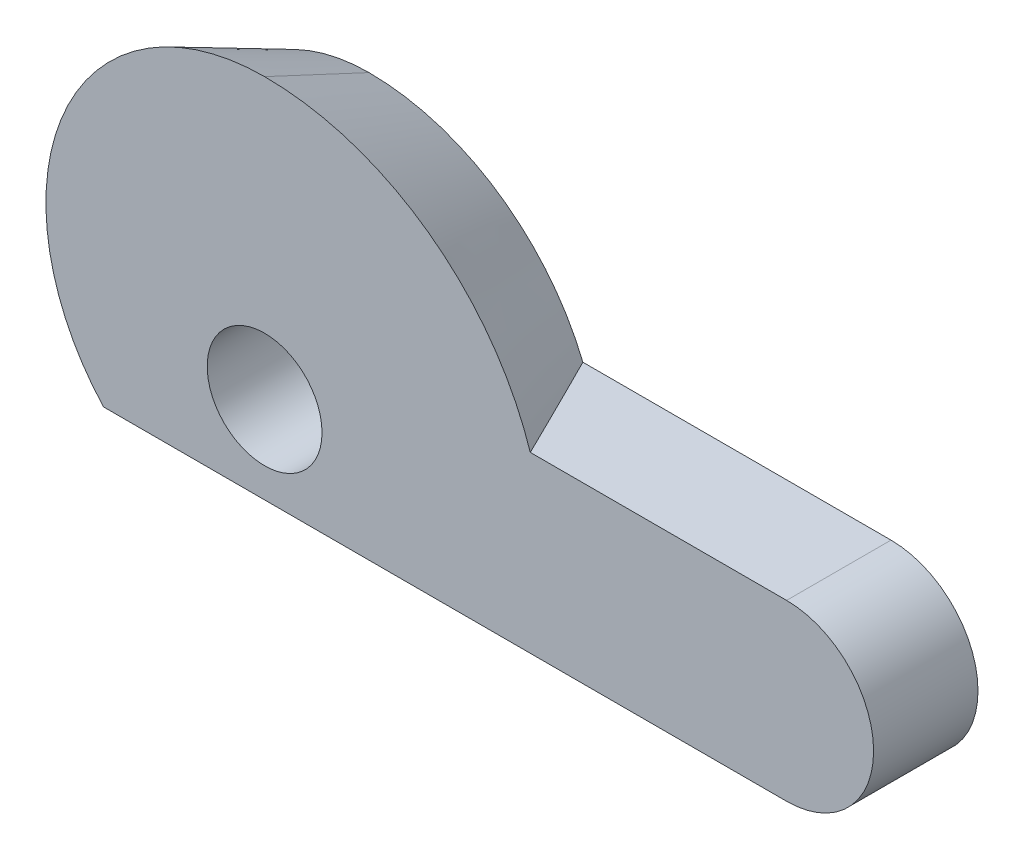
SolidWorks part; units mm, degrees
ref_plane "Plano frontal" through (0, 0, 0) normal (0, 0, 1) x (1, 0, 0)
ref_plane "Plano superior" through (0, 0, 0) normal (0, 1, 0) x (1, 0, 0)
ref_plane "Plano direito" through (0, 0, 0) normal (1, 0, 0) x (0, 0, -1)
sketch "Esboço2" plane through (0, 0, 0) normal (0, 0, 1) x (1, 0, 0)
  line L0 (15, 2.5) -> (8.124, 2.5)
  line L1 (15, -2.5) -> (4.3301, -2.5)
  line L2 (0, 0) -> (0, -5) construction
  line L3 (0, 0) -> (-5, 0) construction
  line L5 (-5.2806, 0) -> (-8.5, 0) construction
  arc A0 (15, -2.5) -> (15, 2.5) centre (15, 0) ccw
  circle A1 centre (0, 0) radius 1.65
  circle A2 centre (0, 0) radius 5 construction
  circle A3 centre (0, 0) radius 8.5 construction
  arc A4 (0, 8.5) -> (0, -5) centre (0, 1.75) ccw
  arc A5 (0, 8.5) -> (8.124, 2.5) centre (0, 0) cw
  arc A6 (0, -5) -> (4.3301, -2.5) centre (0, 0) ccw
  spline S0 degree 3 poles (4.3301, -2.5) (4.6958, -3.7346) (-0.8872, -5.2567) (2.4979, -4.9771) (-11.313, -5.0395) (-8.313, -3.1832) (-6.812, 0.9241) (-3.3405, 8.0667) (-0.7946, 8.4778) (2.5404, 8.3761) (5.4161, 6.8241) (7.7178, 4.2775) (8.124, 2.5) knots 0 0 0 0 0.107318 0.196785 0.229802 0.473899 0.513503 0.613354 0.635297 0.72045 0.799755 1 1 1 1 construction
  dimension "D1" = 3.3
  dimension "D2" = 10
  dimension "D3" = 3.5
  dimension "D4" = 2.5
  dimension "D5" = 15
extrude "Ressalto-extrusão1" add sketch "Esboço2" along normal blind 3
chamfer "Chanfro1" distance 4 angle 25 3 edges at (5.0498, 6.8374, 0) (2.5, -4.3301, 0) (-6.75, 1.75, 0) first distance on face at (4.5559, 6.1687, 1.5) first distance on face at (2.3325, -4.0401, 1.5) first distance on face at (-3.375, 1.75, 1.5)
sketch "Esboço3" plane through (0, 0, 3) normal (0, 0, 1) x (1, 0, 0)
  line L0 (1.8912, -2.5) -> (15, -2.5) construction
  line L1 (7.7033, -2.5) -> (-9.1181, -2.5)
  line L2 (7.7033, -2.5) -> (7.7033, -6.3348)
  line L3 (7.7033, -6.3348) -> (-9.1181, -6.3348)
  line L4 (-9.1181, -2.5) -> (-9.1181, -6.3348)
extrude "Corte-extrusão1" cut sketch "Esboço3" against normal blind 5
